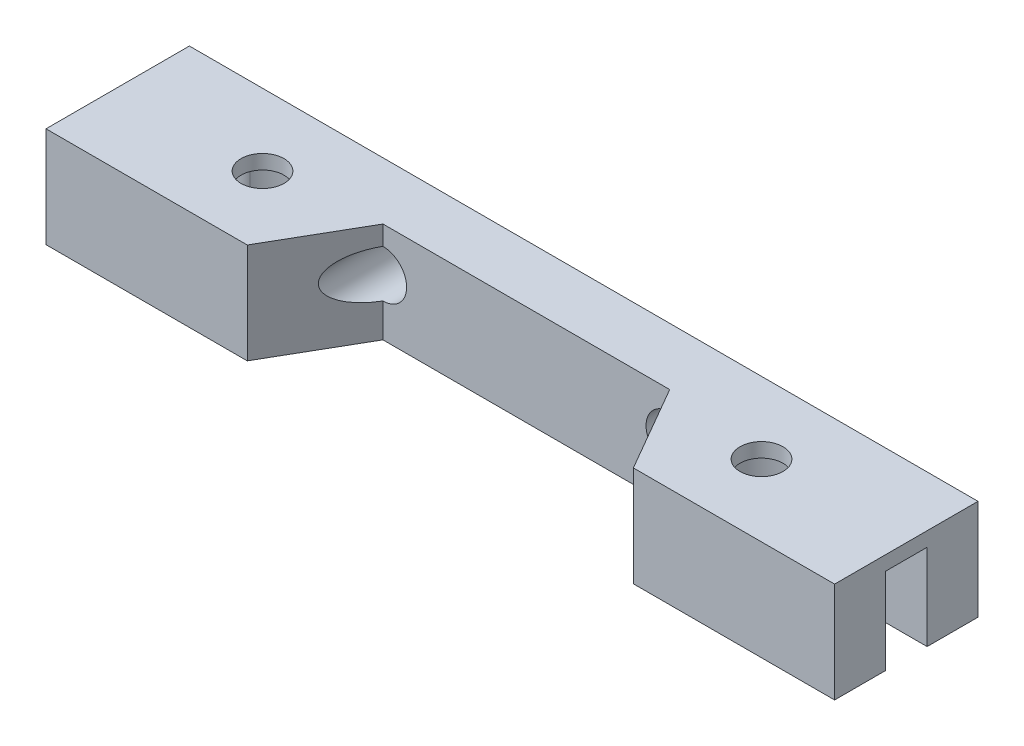
SolidWorks part; units mm, degrees
ref_plane "Front Plane" through (0, 0, 0) normal (0, 0, 1) x (1, 0, 0)
ref_plane "Top Plane" through (0, 0, 0) normal (0, 1, 0) x (1, 0, 0)
ref_plane "Right Plane" through (0, 0, 0) normal (1, 0, 0) x (0, 0, -1)
sketch "Sketch1" plane through (0, 0, 0) normal (0, 1, 0) x (1, 0, 0)
  line L0 (0, 32.6021) -> (0, -31.9538) construction
  line L1 (-17.4, 5) -> (-27.9967, 5) construction
  line L2 (27.5, 10) -> (-27.5, 10)
  line L3 (-20.2526, 6.45) -> (-27.5, 6.45)
  line L4 (-20.2526, 3.55) -> (-27.5, 3.55)
  line L5 (-27.5, 10) -> (-27.5, 6.45)
  line L6 (-27.5, 3.55) -> (-27.5, 0)
  line L7 (27.5, 10) -> (27.5, 6.45)
  line L8 (-27.5, 0) -> (27.5, 0)
  line L9 (-10, 10) -> (-10, 0) construction
  line L10 (-11.7, 10) -> (-11.7, 0) construction
  line L11 (-8.3, 10) -> (-8.3, 0) construction
  line L12 (20.2526, 6.45) -> (27.5, 6.45)
  line L13 (20.2526, 3.55) -> (27.5, 3.55)
  line L14 (27.5, 3.55) -> (27.5, 0)
  arc A1 (-20.2526, 3.55) -> (-20.2526, 6.45) centre (-17.4, 5) ccw
  circle A2 centre (-17.4, 5) radius 4 construction
  arc A3 (20.2526, 3.55) -> (20.2526, 6.45) centre (17.4, 5) cw
  point P23 (-14.2, 5)
  point P27 (0, 10)
  point P30 (0, 0)
  dimension "D2" = 2.9
  dimension "D3" = 6.4
  dimension "D5" = 8
  dimension "D4" = 2.5
  dimension "D6" = 5
  dimension "D7" = 55
  dimension "D8" = 5
  dimension "D9" = 20
  dimension "D10" = 3.4
  dimension "D11" = 55
extrude "Boss-Extrude3" add sketch "Sketch1" along normal blind 3 and the other way blind 3
fillet "Fillet1" radius 0.75 4 edges at (-20.2526, 0, -3.55) (-20.2526, 0, -6.45) (20.2526, 0, -3.55) (20.2526, 0, -6.45)
sketch "Sketch5" plane through (0, 3, 0) normal (0, 1, 0) x (1, 0, 0)
  line L1 (-27.5, 10) -> (27.5, 10)
  line L2 (-27.5, 10) -> (-27.5, 0)
  line L3 (-27.5, 0) -> (27.5, 0)
  line L4 (27.5, 10) -> (27.5, 0)
extrude "Boss-Extrude4" add sketch "Sketch5" along normal blind 1
sketch "Sketch6" plane through (0, 0, -10) normal (0, 0, -1) x (-1, 0, 0)
  line L0 (-27.5, 1) -> (27.5, 1) construction
  line L1 (-27.5, -3) -> (-27.5, 4) construction
  line L2 (27.5, -3) -> (27.5, 4) construction
  line L3 (-27.5, 4) -> (27.5, 4) construction
  line L4 (0, 4) -> (0, -3) construction
  line L5 (-27.5, -3) -> (27.5, -3) construction
  circle A0 centre (-10, 1) radius 1.65
  circle A1 centre (10, 1) radius 1.65
  dimension "D2" = 3.3
  dimension "D1" = 3
  dimension "D3" = 20
extrude "Cut-Extrude2" cut sketch "Sketch6" against normal up to surface (10 mm away) up to face at (0, 0.5, 0)
sketch "Sketch7" plane through (0, 3, 0) normal (0, -1, 0) x (1, 0, 0)
  circle A0 centre (-17.4, -5) radius 1.5
  circle A1 centre (17.4, -5) radius 1.5
  dimension "D1" = 3
  dimension "D2" = 3
extrude "Cut-Extrude3" cut sketch "Sketch7" against normal up to surface (1 mm away) up to face at (0, 4, -5)
sketch "Sketch8" plane through (0, -3, 0) normal (0, -1, 0) x (1, 0, 0)
  line L0 (-13.4641, 0) -> (-10, -6)
  line L1 (-27.5, 0) -> (27.5, 0) construction
  line L2 (-10, -6) -> (10, -6)
  line L3 (0, 0) -> (0, -10) construction
  line L4 (27.5, -10) -> (-27.5, -10) construction
  line L5 (-13.4641, 0) -> (13.4641, 0)
  line L6 (13.4641, 0) -> (10, -6)
  point P11 (0, -6)
  dimension "D1" = 4
  dimension "D2" = 120
  dimension "D3" = 10
extrude "Cut-Extrude4" cut sketch "Sketch8" against normal up to surface (7 mm away) up to face at (-17.4, 4, -3.5)
